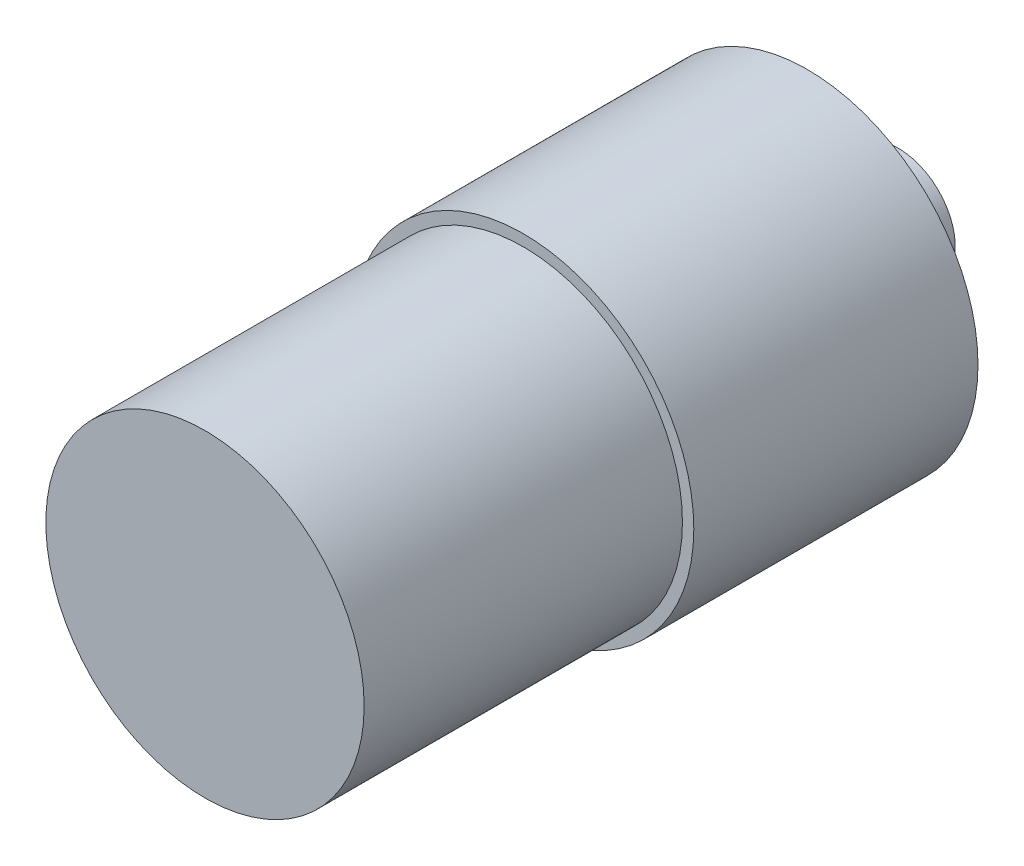
SolidWorks part; units mm, degrees
ref_plane "Front Plane" through (0, 0, 0) normal (0, 0, 1) x (1, 0, 0)
ref_plane "Top Plane" through (0, 0, 0) normal (0, 1, 0) x (1, 0, 0)
ref_plane "Right Plane" through (0, 0, 0) normal (1, 0, 0) x (0, 0, -1)
sketch "Sketch1" plane through (0, 0, 0) normal (0, 0, 1) x (1, 0, 0)
  circle A0 centre (0, 0) radius 15
  dimension "D1" = 30
extrude "Boss-Extrude1" add sketch "Sketch1" along normal blind 25
sketch "Sketch2" plane through (0, 0, 25) normal (0, 0, 1) x (1, 0, 0)
  circle A0 centre (0, 0) radius 14
  dimension "D1" = 28
extrude "Boss-Extrude2" add sketch "Sketch2" along normal blind 28
sketch "Sketch3" plane through (0, 0, 0) normal (0, 0, -1) x (-1, 0, 0)
  circle A0 centre (0, 0) radius 5
  dimension "D1" = 10
extrude "Boss-Extrude3" add sketch "Sketch3" along normal blind 8
hole_wizard "Ø3.3 (3.3) Diameter Hole1" positions "Sketch4" profile "Sketch5" hole size "Ø3.3" standard "ISO"
sketch "Sketch4" plane through (0, 0, -8) normal (0, 0, -1) x (-1, 0, 0)
  point P0 (0, 0)
sketch "Sketch5" plane through (0, 0, -8) normal (1, 0, 0) x (0, 1, 0)
  line L0 (0, 0) -> (0, 8.9914)
  line L1 (0, 8.9914) -> (1.65, 8)
  line L2 (1.65, 8) -> (1.65, 0)
  line L5 (1.65, 0) -> (0, 0)
  line L10 (0, 8.9914) -> (-1.65, 8) construction
  line L11 (0, -6.35) -> (0, 107.95) construction
  dimension "Hole Dia." = 3.3
  dimension "Hole Depth" = 8
  dimension "Drill Angle" = 118
thread "Thread2" pitch 0.7 method cut profile "Thread Profile2" start angle 0, offset 0, length 8, pitch 0.7, diameter 3.3
ref_plane "Plane2" through (1.65, 0, -8) normal (0, -1, 0) x (1, 0, 0)
sketch "Thread Profile2" plane through (1.65, 0, -8) normal (0, -1, 0) x (1, 0, 0)
  line L0 (0, 0) -> (0, 0.7) construction
  line L1 (0, 0) -> (0.3789, 0.2187)
  line L2 (0.3789, 0.2187) -> (0.3789, 0.3062)
  line L3 (0.3789, 0.3062) -> (0, 0.525)
  line L4 (0.3789, 0.2625) -> (0, 0.2625) construction
  line L11 (0, 0) -> (0, 0.525)
  point P2 (0, 0)
  dimension "Pitch" = 0.7
  dimension "Profile_Angle" = 60
  dimension "Profile_Land" = 0.0875
  dimension "Profile_Height" = 0.3789
